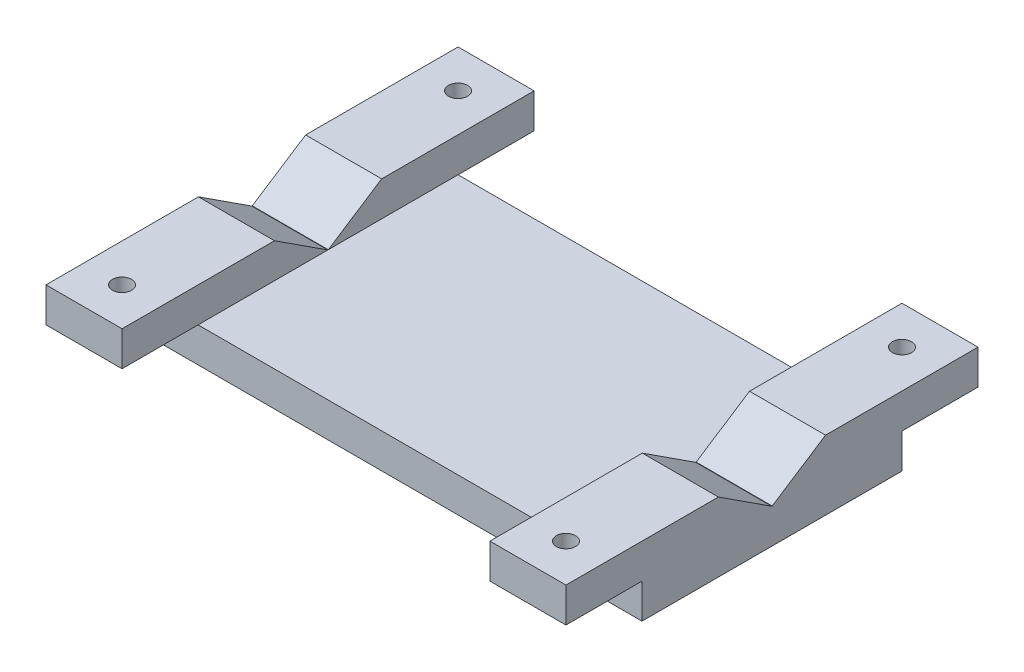
SolidWorks part; units mm, degrees
ref_plane "Front Plane" through (0, 0, 0) normal (0, 0, 1) x (1, 0, 0)
ref_plane "Top Plane" through (0, 0, 0) normal (0, 1, 0) x (1, 0, 0)
ref_plane "Right Plane" through (0, 0, 0) normal (1, 0, 0) x (0, 0, -1)
sketch "Sketch1" plane through (0, 0, 0) normal (0, 1, 0) x (1, 0, 0)
  line L1 (30, -15) -> (-30, -15)
  line L2 (30, -15) -> (30, 15)
  line L3 (30, 15) -> (-30, 15)
  line L4 (-30, -15) -> (-30, 15)
  line L5 (30, -15) -> (-30, 15) construction
  line L6 (30, 15) -> (-30, -15) construction
  point P0 (0, 0)
  dimension "D1" = 30
  dimension "D2" = 60
extrude "Boss-Extrude1" add sketch "Sketch1" along normal blind 4
sketch "Sketch2" plane through (0, 4, 0) normal (0, 1, 0) x (1, 0, 0)
  line L0 (30, 15) -> (-30, 15) construction
  line L1 (-21.2248, 23.7752) -> (-30, 23.7752)
  line L2 (-21.2248, 23.7752) -> (-21.2248, 6.2248)
  line L3 (-21.2248, 6.2248) -> (-30, 6.2248)
  line L4 (-30, 23.7752) -> (-30, 6.2248)
  line L5 (-21.2248, 23.7752) -> (-30, 6.2248) construction
  line L6 (-21.2248, 6.2248) -> (-30, 23.7752) construction
  line L7 (-30, 15) -> (-30, -15) construction
  line L8 (-30, 0) -> (0, 0) construction
  line L9 (0, 0) -> (0, 15) construction
  line L10 (-30, -23.7752) -> (-30, -6.2248)
  line L11 (-21.2248, -6.2248) -> (-30, -6.2248)
  line L12 (-21.2248, -23.7752) -> (-21.2248, -6.2248)
  line L13 (-21.2248, -23.7752) -> (-30, -23.7752)
  line L14 (21.2248, -23.7752) -> (30, -23.7752)
  line L15 (21.2248, -23.7752) -> (21.2248, -6.2248)
  line L16 (21.2248, -6.2248) -> (30, -6.2248)
  line L17 (30, -23.7752) -> (30, -6.2248)
  line L18 (30, 23.7752) -> (30, 6.2248)
  line L19 (21.2248, 6.2248) -> (30, 6.2248)
  line L20 (21.2248, 23.7752) -> (21.2248, 6.2248)
  line L21 (21.2248, 23.7752) -> (30, 23.7752)
  line L22 (-25.6124, 15) -> (-25.6124, 23.7752) construction
  circle A0 centre (-25.6124, 19.3876) radius 1.1
  circle A1 centre (25.6124, 19.3876) radius 1.1
  circle A2 centre (25.6124, -19.3876) radius 1.1
  circle A3 centre (-25.6124, -19.3876) radius 1.1
  point P0 (-25.6124, 15)
  point P11 (-25.6124, -15)
  point P18 (25.6124, -15)
  point P19 (25.6124, 15)
  dimension "D2" = 2.2
  dimension "D1" = 8.7752
extrude "Boss-Extrude2" add sketch "Sketch2" along normal blind 4
chamfer "Chamfer1" distance 6.2 angle 33 4 edges at (25.6124, 4, -6.2248) (25.6124, 4, 6.2248) (-25.6124, 4, 6.2248) first distance on face at (-0.3656, 4, -0.5187)
